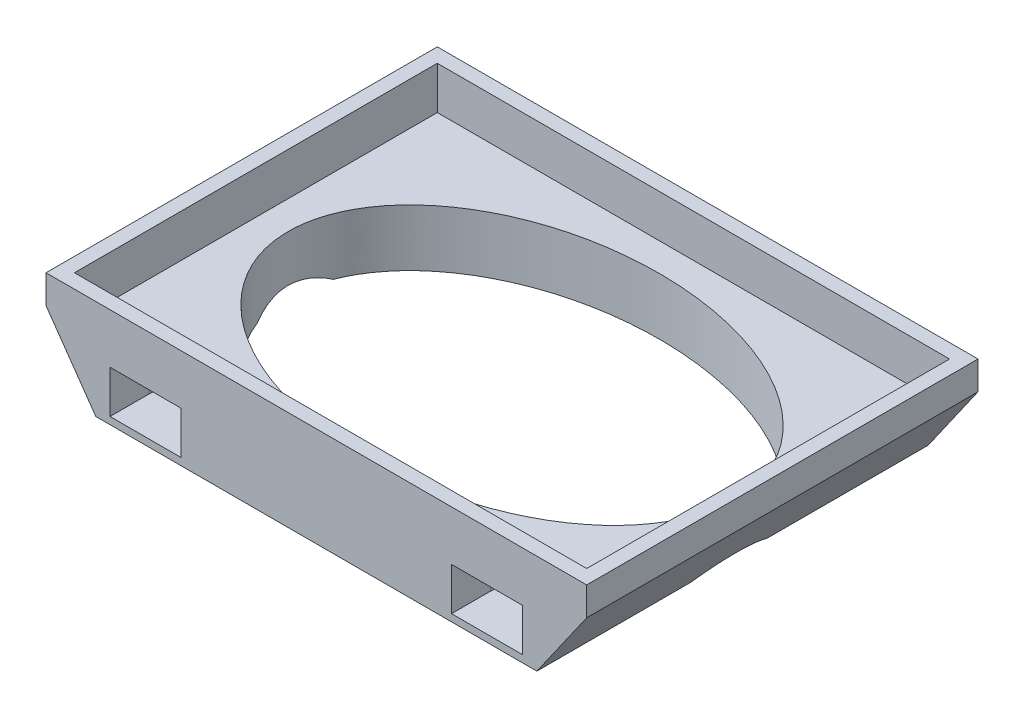
SolidWorks part; units mm, degrees
ref_plane "Front Plane" through (0, 0, 0) normal (0, 0, 1) x (1, 0, 0)
ref_plane "Top Plane" through (0, 0, 0) normal (0, 1, 0) x (1, 0, 0)
ref_plane "Right Plane" through (0, 0, 0) normal (1, 0, 0) x (0, 0, -1)
sketch "Sketch1" plane through (0, 0, 0) normal (0, 1, 0) x (1, 0, 0)
  line L0 (-36.5297, 0) -> (34.0127, 0) construction
  line L1 (0, -19.8975) -> (0, 26.8361) construction
  line L3 (-19, -13.75) -> (19, -13.75)
  line L4 (-19, -13.75) -> (-19, 13.75)
  line L5 (-19, 13.75) -> (19, 13.75)
  line L6 (19, -13.75) -> (19, 13.75)
  dimension "D1" = 27.5
  dimension "D2" = 38
  dimension "D3" = 13.75
  dimension "D4" = 19
extrude "Boss-Extrude1" add sketch "Sketch1" against normal blind 7
sketch "Sketch2" plane through (0, 0, 0) normal (0, 1, 0) x (1, 0, 0)
  line L0 (-19, 13.75) -> (-19, -13.75) construction
  line L1 (-18, 12.75) -> (18, 12.75)
  line L2 (-18, 12.75) -> (-18, -12.75)
  line L3 (-18, -12.75) -> (18, -12.75)
  line L4 (18, 12.75) -> (18, -12.75)
  line L5 (19, -13.75) -> (19, 13.75) construction
  line L6 (19, 13.75) -> (-19, 13.75) construction
  line L7 (-19, -13.75) -> (19, -13.75) construction
  dimension "D1" = 1
  dimension "D2" = 1
  dimension "D3" = 1
  dimension "D4" = 1
extrude "Cut-Extrude1" cut sketch "Sketch2" against normal blind 3
sketch "Sketch3" plane through (0, -3, 0) normal (0, 1, 0) x (1, 0, 0)
  line L14 (-19, 13.75) -> (-19, -13.75) construction
  line L15 (-19, -13.75) -> (19, -13.75) construction
  ellipse E0 centre (0, 0) end of major axis (16, -0.498) minor radius 10.7552
  dimension "D1" = 3
  dimension "D2" = 3
extrude "Cut-Extrude2" cut sketch "Sketch3" against normal through all both and the other way through all
sketch "Sketch4" plane through (0, 0, 0) normal (0, 1, 0) x (1, 0, 0)
  line L0 (-25.2485, 0) -> (37.2083, 0) construction
  line L1 (0, -20.0379) -> (0, 20.8772) construction
ref_axis "Axis1" through (0, 0, 20.0379) along (0, 0, -1)
ref_axis "Axis2" through (-25.2485, 0, 0) along (1, 0, 0)
sketch "Sketch7" plane through (0, -7, 0) normal (0, 1, 0) x (1, 0, 0)
  line L5 (-19, -13.75) -> (-9, -13.75)
  line L6 (-19, -13.75) -> (-19, -4.736)
  line L7 (-19, -4.736) -> (-9, -4.736)
  line L8 (-9, -13.75) -> (-9, -4.736)
  line L9 (-19, 13.75) -> (-9, 13.75)
  line L10 (-19, 13.75) -> (-19, 3.75)
  line L11 (-19, 3.75) -> (-9, 3.75)
  line L12 (-9, 13.75) -> (-9, 3.75)
  line L13 (19, 13.75) -> (9, 13.75)
  line L14 (19, 13.75) -> (19, 3.75)
  line L15 (19, 3.75) -> (9, 3.75)
  line L16 (9, 13.75) -> (9, 3.75)
  line L17 (19, -13.75) -> (9, -13.75)
  line L18 (19, -13.75) -> (19, -3.75)
  line L19 (19, -3.75) -> (9, -3.75)
  line L20 (9, -13.75) -> (9, -3.75)
  dimension "D1" = 10
  dimension "D2" = 10
  dimension "D3" = 10
  dimension "D4" = 10
  dimension "D5" = 10
  dimension "D6" = 10
  dimension "D7" = 10
extrude "Cut-Extrude3" [suppressed] cut sketch "Sketch7" along normal blind 1
ref_plane "Plane1" through (0, -5, 0) normal (0, -1, 0) x (-1, 0, 0)
sketch "Sketch8" plane through (0, -5, 0) normal (0, -1, 0) x (-1, 0, 0)
  line L0 (-14.5, 11) -> (-14.5, 23.5627)
  line L1 (-14.5, 23.5627) -> (-9.5, 23.5627)
  line L2 (-9.5, 23.5627) -> (-9.5, 11)
  line L3 (-14.5, 11) -> (-9.5, 11) construction
  line L4 (0, -20.0379) -> (0, 20.8772) construction
  line L5 (25.2485, 0) -> (-37.2083, 0) construction
  line L6 (0, 39.7599) -> (0, -34.6026) construction
  line L7 (-51.5772, 0) -> (38.0826, 0) construction
  line L8 (9.5, 23.5627) -> (9.5, 11)
  line L9 (14.5, 11) -> (14.5, 23.5627)
  line L10 (14.5, 23.5627) -> (9.5, 23.5627)
  line L11 (14.5, -11) -> (14.5, -23.5627)
  line L12 (14.5, -23.5627) -> (9.5, -23.5627)
  line L13 (9.5, -23.5627) -> (9.5, -11)
  line L14 (-9.5, -23.5627) -> (-9.5, -11)
  line L15 (-14.5, -23.5627) -> (-9.5, -23.5627)
  line L16 (-14.5, -11) -> (-14.5, -23.5627)
  arc A1 (14.5, 11) -> (9.5, 11) centre (12, 11) cw
  arc A2 (-14.5, 11) -> (-9.5, 11) centre (-12, 11) ccw
  arc A3 (14.5, -11) -> (9.5, -11) centre (12, -11) ccw
  arc A4 (-14.5, -11) -> (-9.5, -11) centre (-12, -11) cw
  dimension "D1" = 2.5
  dimension "D2" = 90
  dimension "D3" = 12
  dimension "D4" = 11
extrude "Cut-Extrude4" cut sketch "Sketch8" against normal mid plane 3
sketch "Sketch9" plane through (0, 0, 0) normal (0, 0, 1) x (1, 0, 0)
  line L0 (-15.499, -7) -> (-19, -2)
  line L1 (-19, -7) -> (19, -7) construction
  line L2 (-19, -7) -> (-19, 0) construction
  line L3 (-19, -2) -> (-19, -7)
  line L4 (-19, -7) -> (-15.499, -7)
  line L5 (0, 8.3975) -> (0, -16.9982) construction
  line L6 (-25.2485, 0) -> (37.2083, 0) construction
  line L7 (19, -7) -> (15.499, -7)
  line L8 (19, -2) -> (19, -7)
  line L9 (15.499, -7) -> (19, -2)
  dimension "D1" = 2
  dimension "D2" = 35
extrude "Cut-Extrude5" cut sketch "Sketch9" against normal through all both and the other way through all
